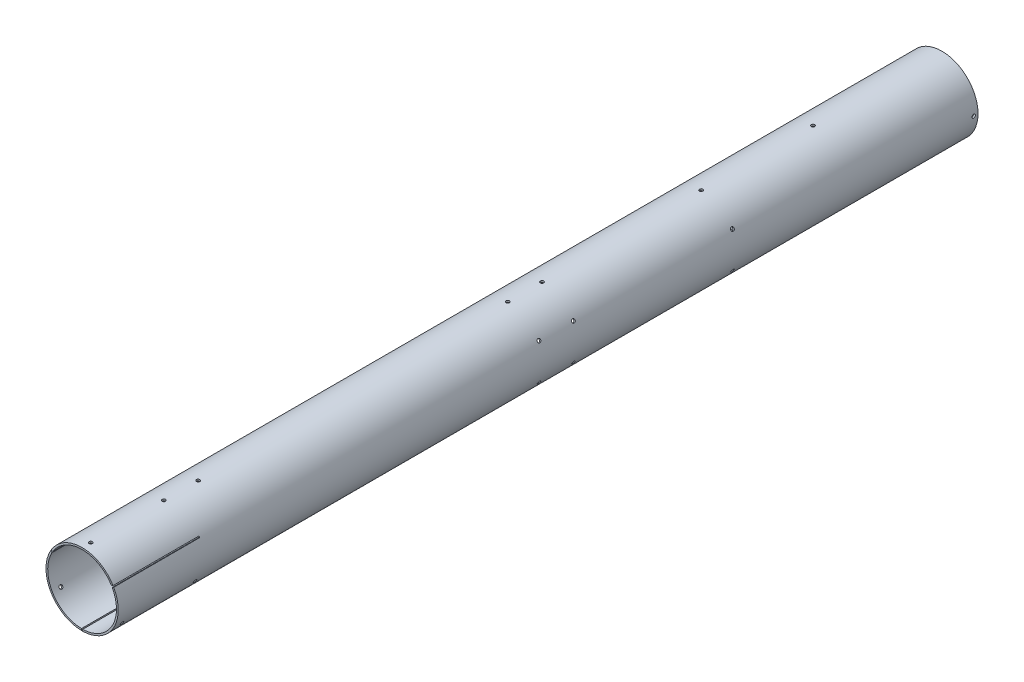
SolidWorks part; units mm, degrees
ref_plane "Front Plane" through (0, 0, 0) normal (0, 0, 1) x (1, 0, 0)
ref_plane "Top Plane" through (0, 0, 0) normal (0, 1, 0) x (1, 0, 0)
ref_plane "Right Plane" through (0, 0, 0) normal (1, 0, 0) x (0, 0, -1)
sketch "Sketch1" plane through (0, 0, 0) normal (0, 0, 1) x (1, 0, 0)
  circle A0 centre (0, 0) radius 40
  circle A1 centre (0, 0) radius 42
  dimension "D1" = 84
  dimension "D2" = 80
extrude "Boss-Extrude1" add sketch "Sketch1" along normal blind 1000
sketch "Sketch2" plane through (0, 0, 0) normal (0, 1, 0) x (1, 0, 0)
  line L0 (-42, -1000) -> (42, -1000) construction
  line L1 (-42, -1000) -> (42, -1000)
  line L2 (-0.75, -1000) -> (-0.75, -900)
  line L3 (-0.75, -900) -> (0.75, -900)
  line L4 (0.75, -900) -> (0.75, -1000)
  line L5 (-0.75, -1000) -> (0.75, -1000)
  point P4 (0, -900)
  point P6 (0, -1000)
  dimension "D1" = 100
  dimension "D2" = 1.5
extrude "Cut-Extrude1" cut sketch "Sketch2" against normal through all contours L4 L5 L2 L3
ref_axis "Axis1" through (0, 0, 525) along (0, 0, -1)
pattern_circular "CirPattern1" count 3 over 360 about axis through (0, 0, 525) along (0, 0, -1) of "Cut-Extrude1"
sketch "Sketch5" plane through (0, 0, 0) normal (0, 1, 0) x (1, 0, 0)
  line L0 (-42, -990) -> (42, -990) construction
  line L1 (-42, 0) -> (-42, -1000) construction
  line L2 (42, -1000) -> (42, 0) construction
  line L3 (42, -905) -> (-42, -905) construction
  line L4 (-35.9923, -1000) -> (35.9923, -1000) construction
  line L5 (42, -280) -> (-42, -280) construction
  line L6 (42, -1000) -> (42, 0) construction
  line L7 (-42, 0) -> (-42, -1000) construction
  line L8 (40, 0) -> (-40, 0) construction
  line L9 (42, -505) -> (-42, -505) construction
  line L10 (42, -465) -> (-42, -465) construction
  line L11 (-42, -150) -> (42, -150) construction
  line L12 (42, -865) -> (-42, -865) construction
  line L13 (-42, -5) -> (42, -5) construction
  line L14 (42, 0) -> (-42, 0) construction
  circle A0 centre (0, -905) radius 2
  circle A1 centre (0, -990) radius 2
  circle A2 centre (0, -280) radius 2
  circle A3 centre (0, -505) radius 2
  circle A4 centre (0, -465) radius 2
  circle A5 centre (0, -150) radius 2
  circle A6 centre (0, -865) radius 2
  circle A7 centre (0, -5) radius 2
  point P26 (0, -150)
  point P44 (0, -5)
  dimension "D3" = 4
  dimension "D5" = 4
  dimension "D6" = 4
  dimension "D8" = 4
  dimension "D12" = 4
  dimension "D13" = 4
  dimension "D15" = 4
  dimension "D1" = 10
  dimension "D2" = 5
  dimension "D4" = 280
  dimension "D7" = 495
  dimension "D9" = 0
  dimension "D10" = 40
  dimension "D11" = 150
  dimension "D14" = 40
  dimension "D16" = 5
extrude "Cut-Extrude3" cut sketch "Sketch5" along normal through all contours A1 | A0 region at (0, 0, 905) region at (0, 0, 990)
pattern_circular "CirPattern3" count 3 over 360 about axis through (0, 0, 525) along (0, 0, -1) of "Cut-Extrude3"
extrude "Cut-Extrude4" cut sketch "Sketch5<3>" along normal through all contours A3 | A4 | A2 region at (0, 0, 280) region at (0, 0, 505) region at (0, 0, 465)
sketch "Sketch5<3>" plane through (0, 0, 0) normal (0, 1, 0) x (1, 0, 0) same geometry as "Sketch5"
pattern_circular "CirPattern4" count 6 over 360 about axis through (0, 0, 525) along (0, 0, -1) of "Cut-Extrude4"
extrude "Cut-Extrude5" cut sketch "Sketch5<5>" along normal through all contours A5 | A6 region at (0, 0, 150) region at (0, 0, 865)
sketch "Sketch5<5>" plane through (0, 0, 0) normal (0, 1, 0) x (1, 0, 0) same geometry as "Sketch5"
sketch "Sketch7" plane through (0, 0, 0) normal (1, 0, 0) x (0, 0, -1)
  line L0 (-5, 42) -> (-5, -42) construction
  line L1 (0, 42) -> (-148, 42) construction
  line L2 (-278.0001, -42) -> (0, -42) construction
  line L3 (0, -42) -> (0, 42) construction
  circle A0 centre (-5, 0) radius 2
  dimension "D2" = 4
  dimension "D1" = 5
extrude "Cut-Extrude6" cut sketch "Sketch7" against normal through all both and the other way through all
sketch "Sketch6" plane through (0, 0, 0) normal (0, 1, 0) x (1, 0, 0)
  line L0 (-35.9923, -1000) -> (35.9923, -1000) construction
  line L1 (27.5, -225) -> (-27.5, -225)
  line L2 (27.5, -225) -> (27.5, -475)
  line L3 (27.5, -475) -> (-27.5, -475)
  line L4 (-27.5, -225) -> (-27.5, -475)
  line L5 (0, -525) -> (0, 25) construction
  point P8 (0, -475)
  dimension "D1" = 525
  dimension "D2" = 250
  dimension "D3" = 55
extrude "Cut-Extrude7" cut sketch "Sketch6" against normal through all
